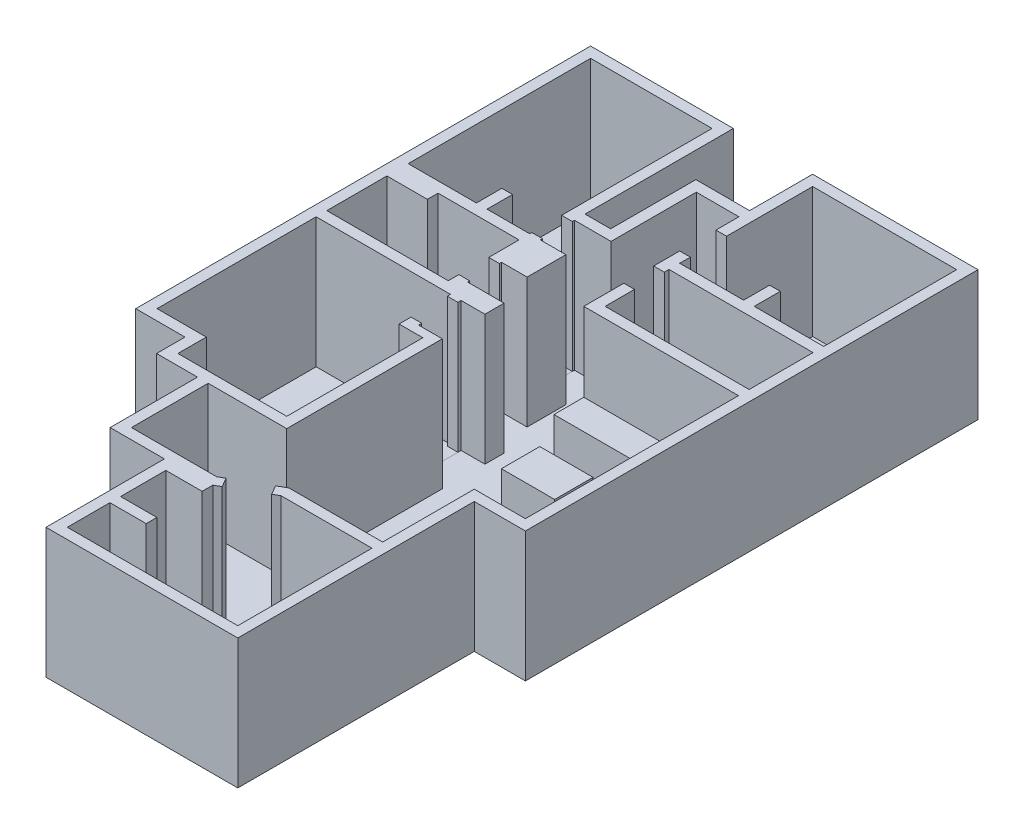
SolidWorks part; units mm, degrees
other "Long Room Closet"
other "Window Room Closet"
other "Walls"
other "Window Room"
other "Big Room"
other "Bathroom 1"
other "Corner Room"
other "Long Room"
other "Bathroom 2"
other "Big Room Closet"
other "Corner Room Closet"
ref_plane "Front Plane" through (0, 0, 0) normal (0, 0, 1) x (1, 0, 0)
ref_plane "Top Plane" through (0, 0, 0) normal (0, 1, 0) x (1, 0, 0)
ref_plane "Right Plane" through (0, 0, 0) normal (1, 0, 0) x (0, 0, -1)
sketch "Sketch1" plane through (0, 0, 0) normal (0, 1, 0) x (1, 0, 0)
  line L0 (0, 0) -> (0, -4280)
  line L1 (0, 0) -> (8590, 0) construction
  line L2 (0, 0) -> (0, -15669) construction
  line L3 (0, -15669) -> (8590, -15669) construction
  line L4 (8590, 0) -> (8590, -15669) construction
  line L5 (0, -4280) -> (1600, -4280)
  line L6 (1600, -4280) -> (1600, -3683)
  line L7 (1600, -3683) -> (1850, -3683)
  line L8 (2850, 0) -> (2850, -3530)
  line L9 (2850, -3530) -> (3100, -3530)
  line L11 (6710, -2510) -> (6710, -3120)
  line L12 (6710, -3120) -> (5210, -3120)
  line L13 (5210, -3480) -> (5210, -3370)
  line L14 (2850, 0) -> (0, 0)
  line L15 (5210, 0) -> (8590, 0)
  line L16 (8590, 0) -> (8590, -3120)
  line L17 (4241, -13106.5805) -> (4241, -13356.5805)
  line L18 (4116, -12890.0742) -> (4255.9329, -12809.2839)
  line L22 (8590, -3370) -> (8590, -4870)
  line L23 (5210, -4870) -> (8590, -4870)
  line L25 (0, -6190) -> (2850, -6190)
  line L26 (2850, -6190) -> (2850, -5940)
  line L27 (2850, -4530) -> (950, -4530)
  line L28 (0, -4780) -> (0, -6190)
  line L29 (950, -4530) -> (950, -4780)
  line L30 (1600, -3683) -> (0, -3683)
  line L31 (4255.9329, -12809.2839) -> (4380.9329, -13025.7903)
  line L32 (4241, -14419) -> (3390, -14419)
  line L33 (1850, -3683) -> (1850, -4280)
  line L34 (1850, -4280) -> (2850, -4280)
  line L35 (2850, -4280) -> (2850, -4230)
  line L36 (2850, -4230) -> (3100, -4230)
  line L37 (3100, -4230) -> (3100, -4280)
  line L38 (3100, -4280) -> (3700, -4280)
  line L39 (3100, -3530) -> (3100, -3480)
  line L40 (3100, -3480) -> (3960, -3480)
  line L41 (3960, -3480) -> (3960, -1480)
  line L42 (3960, -1480) -> (4960, -1480)
  line L43 (4960, -1480) -> (4960, -2020)
  line L45 (5210, -3120) -> (5210, -2870)
  line L46 (5210, -2870) -> (4960, -2870)
  line L47 (4960, -2870) -> (4960, -3480)
  line L48 (4960, -3480) -> (5210, -3480)
  line L49 (5210, -3480) -> (5210, -3370)
  line L50 (5210, -3370) -> (8590, -3370)
  line L51 (3700, -4280) -> (3700, -5190)
  line L52 (4960, -4180) -> (5210, -4180)
  line L53 (5210, -4180) -> (5210, -4870)
  line L54 (4960, -4180) -> (4960, -5120)
  line L55 (4960, -5120) -> (8590, -5120)
  line L56 (3700, -5190) -> (3100, -5190)
  line L57 (3100, -5190) -> (3100, -5240)
  line L58 (3100, -5240) -> (2850, -5240)
  line L59 (2850, -5240) -> (2850, -4530)
  line L60 (2850, -5940) -> (3100, -5940)
  line L61 (950, -4780) -> (0, -4780)
  line L62 (3100, -5940) -> (3100, -5990)
  line L63 (3100, -5990) -> (3960, -5990)
  line L64 (3960, -5990) -> (3960, -6440)
  line L65 (3960, -6440) -> (3401.2, -6440)
  line L66 (3401.2, -6440) -> (3401.2, -6515)
  line L67 (3401.2, -6515) -> (3151.2, -6515)
  line L68 (3151.2, -6515) -> (3151.2, -6440)
  line L69 (3151.2, -6440) -> (0, -6440)
  line L70 (1155.7, -10840.0742) -> (3710, -10840.0742)
  line L71 (3401.2, -7440) -> (3401.2, -7365)
  line L72 (3401.2, -7440) -> (3960, -7440)
  line L73 (3960, -7440) -> (3960, -11090.0742)
  line L74 (4380.9329, -13025.7903) -> (4241, -13106.5805)
  line L75 (3390, -14669) -> (4241, -14669)
  line L77 (4241, -14419) -> (4241, -14669)
  line L78 (3390, -14669) -> (3390, -15669)
  line L79 (3401.2, -7365) -> (3151.2, -7365)
  line L80 (3151.2, -7365) -> (3151.2, -7646.5)
  line L81 (3151.2, -7646.5) -> (3710, -7646.5)
  line L82 (3710, -7646.5) -> (3710, -10840.0742)
  line L83 (4116, -12890.0742) -> (2116, -12890.0742)
  line L84 (3960, -11090.0742) -> (2116, -11090.0742)
  line L86 (5117.0544, -12600.7903) -> (4992.0544, -12384.2839)
  line L89 (4992.0544, -12384.2839) -> (5190, -12270)
  line L90 (5190, -12270) -> (7390, -12270)
  line L91 (4255.9329, -12809.2839) -> (4992.0544, -12384.2839)
  line L92 (5117.0544, -12600.7903) -> (5256.9873, -12520)
  line L93 (5256.9873, -12520) -> (7390, -12520)
  line L94 (4241, -13356.5805) -> (3390, -13356.5805)
  line L95 (3390, -13356.5805) -> (3390, -14419)
  line L96 (4241, -13356.5805) -> (4241, -14419)
  line L97 (2116, -12890.0742) -> (2116, -11090.0742)
  line L98 (6710, -2510) -> (6960, -2510)
  line L99 (6960, -2510) -> (6960, -3120)
  line L100 (6960, -3120) -> (8590, -3120)
  line L101 (6960, -2510) -> (8590, -2510)
  line L102 (5210, -2020) -> (4960, -2020)
  line L103 (5210, -2020) -> (5210, 0)
  line L104 (4960, -2870) -> (4960, -3480)
  line L105 (5210, -3120) -> (5210, -2870)
  line L106 (8590, -5120) -> (8590, -10120)
  line L107 (8590, -10120) -> (7390, -10120)
  line L108 (7390, -10120) -> (7390, -12270)
  line L109 (7390, -12520) -> (7390, -15669)
  line L110 (7390, -15669) -> (3390, -15669)
  line L111 (4241, -13106.5805) -> (4116, -12890.0742) construction
  line L112 (3710, -10173.8) -> (0, -10173.8)
  line L113 (1155.7, -10840.0742) -> (1155.7, -10173.8)
  line L114 (0, -6440) -> (0, -10173.8)
  line L115 (1155.7, -10173.8) -> (0, -10173.8)
  line L116 (3401.2, -7365) -> (3401.2, -6515)
  line L117 (3100, -5940) -> (3100, -5240)
  line L118 (3100, -4230) -> (3100, -3530)
  line L119 (4960, -2870) -> (4960, -2020)
  line L120 (4960, -4180) -> (4960, -3480)
  dimension "D1" = 2850
  dimension "D2" = 150
  dimension "D3" = 4280
  dimension "D4" = 800
  dimension "D5" = 1000
  dimension "D6" = 600
  dimension "D7" = 860
  dimension "D8" = 1000
  dimension "D9" = 2000
  dimension "D10" = 250
  dimension "D11" = 250
  dimension "D12" = 250
  dimension "D13" = 558.8
  dimension "D14" = 250
  dimension "D15" = 250
  dimension "D16" = 3120
  dimension "D17" = 250
  dimension "D18" = 700
  dimension "D19" = 850
  dimension "D20" = 700
  dimension "D21" = 1500
  dimension "D22" = 3380
  dimension "D23" = 250
  dimension "D24" = 1500
  dimension "D25" = 1660
  dimension "D26" = 250
  dimension "D27" = 1206.5
  dimension "D28" = 5000
  dimension "D29" = 1000
  dimension "D30" = 250
  dimension "D31" = 3683
  dimension "D32" = 2510
  dimension "D33" = 450
  dimension "D34" = 250
  dimension "D35" = 4000
  dimension "D36" = 250
  dimension "D37" = 250
  dimension "D38" = 1200
  dimension "D39" = 2150
  dimension "D40" = 3149
  dimension "D41" = 3149
  dimension "D42" = 850
  dimension "D43" = 1000
  dimension "D44" = 250
  dimension "D45" = 2200
  dimension "D46" = 2000
  dimension "D47" = 1800
  dimension "D48" = 250
  dimension "D49" = 250
  dimension "D50" = 1900
  dimension "D51" = 700
  dimension "D52" = 250
  dimension "D53" = 850
  dimension "D54" = 2527.3
  dimension "D55" = 1155.7
extrude "Boss-Extrude1" add sketch "Sketch1" along normal blind 100 contours L36 L118 L9 L8 L14 L0 L5 L6 L7 L33 L34 L35 | L119 L46 L45 L12 L11 L98 L99 L100 L16 L15 L103 L102 | L60 L117 L58 L59 L27 L29 L61 L28 L25 L26 | L79 L116 L67 L68 L69 L114 L115 L113 L70 L82 L81 L80 | L110 L109 L93 L92 L86 L91 L31 L74 L17 L94 L95 L32 L77 L75 L78 | L120 L52 L53 L23 L22 L50 L13 L48 region at (1498.0773, 0, 1986.5335) region at (6770.383, 0, 1429.8229) region at (1531.4314, 0, 5404.487) region at (6839.4423, 0, 4110.3241) region at (1798.2254, 0, 8348.8303) region at (5668.1773, 0, 14190.9305)
extrude "Boss-Extrude2" add sketch "Sketch1<4>" along normal blind 100 separate body contours L54 L120 L47 L119 L43 L42 L41 L40 L39 L118 L37 L38 L51 L56 L57 L117 L62 L63 L64 L65 L66 L116 L71 L72 L73 L84 L97 L83 L18 L91 L89 L90 L108 L107 L106 L55 region at (5566.5772, 0, 8174.0459)
sketch "Sketch1<4>" plane through (0, 0, 0) normal (0, 1, 0) x (1, 0, 0) same geometry as "Sketch1"
extrude "Boss-Extrude4" add sketch "Sketch1<5>" along normal blind 100 separate body contours L6 L30 L0 L5 | L101 L99 L100 L16 | L113 L70 L82 L112 | L96 L94 L95 L32 region at (800, 0, 3981.5) region at (7775, 0, 2815) region at (2432.85, 0, 10506.9371) region at (3815.5, 0, 13887.7903)
sketch "Sketch1<5>" plane through (0, 0, 0) normal (0, 1, 0) x (1, 0, 0) same geometry as "Sketch1"
sketch "Sketch2" plane through (0, 100, 0) normal (0, 1, 0) x (1, 0, 0)
  line L0 (5210, -2020) -> (4960, -2020) construction
  line L1 (5210, -2020) -> (5210, 0) construction
  line L2 (5210, 0) -> (8590, 0) construction
  line L3 (8590, 0) -> (8590, -3120) construction
  line L4 (6960, -3120) -> (8590, -3120) construction
  line L5 (6960, -2510) -> (6960, -3120) construction
  line L6 (6710, -2510) -> (6960, -2510) construction
  line L7 (6710, -2510) -> (6710, -3120) construction
  line L8 (6710, -3120) -> (5210, -3120) construction
  line L9 (5210, -3120) -> (5210, -2870) construction
  line L10 (5210, -3120) -> (5210, -2870) construction
  line L11 (2850, -3530) -> (3100, -3530) construction
  line L12 (2850, 0) -> (2850, -3530) construction
  line L13 (2850, 0) -> (0, 0) construction
  line L14 (0, 0) -> (0, -4280) construction
  line L15 (0, -4280) -> (1600, -4280) construction
  line L16 (1600, -4280) -> (1600, -3683) construction
  line L17 (1600, -3683) -> (1850, -3683) construction
  line L18 (1850, -3683) -> (1850, -4280) construction
  line L19 (1850, -4280) -> (2850, -4280) construction
  line L20 (2850, -4280) -> (2850, -4230) construction
  line L21 (2850, -4230) -> (3100, -4230) construction
  line L22 (3100, -3530) -> (3100, -3480) construction
  line L23 (3100, -3480) -> (3960, -3480) construction
  line L24 (3960, -3480) -> (3960, -1480) construction
  line L25 (3960, -1480) -> (4960, -1480) construction
  line L26 (4960, -1480) -> (4960, -2020) construction
  line L27 (3100, -4230) -> (3100, -3530) construction
  line L28 (4116, -12890.0742) -> (4255.9329, -12809.2839) construction
  line L29 (4116, -12890.0742) -> (2116, -12890.0742) construction
  line L30 (2116, -12890.0742) -> (2116, -11090.0742) construction
  line L31 (3960, -11090.0742) -> (2116, -11090.0742) construction
  line L32 (3960, -7440) -> (3960, -11090.0742) construction
  line L33 (3401.2, -7440) -> (3960, -7440) construction
  line L34 (3401.2, -7440) -> (3401.2, -7365) construction
  line L35 (4255.9329, -12809.2839) -> (4380.9329, -13025.7903) construction
  line L36 (4380.9329, -13025.7903) -> (4241, -13106.5805) construction
  line L37 (4241, -13106.5805) -> (4241, -13356.5805) construction
  line L38 (4241, -13356.5805) -> (3390, -13356.5805) construction
  line L39 (3390, -13356.5805) -> (3390, -14419) construction
  line L40 (4241, -14419) -> (3390, -14419) construction
  line L41 (4241, -14419) -> (4241, -14669) construction
  line L42 (3390, -14669) -> (4241, -14669) construction
  line L43 (3390, -14669) -> (3390, -15669) construction
  line L44 (7390, -15669) -> (3390, -15669) construction
  line L45 (7390, -12520) -> (7390, -15669) construction
  line L46 (5256.9873, -12520) -> (7390, -12520) construction
  line L47 (5117.0544, -12600.7903) -> (5256.9873, -12520) construction
  line L48 (5117.0544, -12600.7903) -> (4992.0544, -12384.2839) construction
  line L49 (4255.9329, -12809.2839) -> (4992.0544, -12384.2839) construction
  line L50 (4960, -2870) -> (4960, -3480) construction
  line L51 (4960, -3480) -> (5210, -3480) construction
  line L52 (4960, -2870) -> (4960, -3480) construction
  line L53 (4960, -4180) -> (4960, -3480) construction
  line L54 (5210, -2870) -> (4960, -2870) construction
  line L55 (4960, -2870) -> (4960, -2020) construction
  line L56 (3100, -4230) -> (3100, -4280) construction
  line L57 (3100, -4280) -> (3700, -4280) construction
  line L58 (3700, -4280) -> (3700, -5190) construction
  line L59 (3700, -5190) -> (3100, -5190) construction
  line L60 (3100, -5190) -> (3100, -5240) construction
  line L61 (5210, -3480) -> (5210, -3370) construction
  line L62 (5210, -3480) -> (5210, -3370) construction
  line L63 (4960, -4180) -> (5210, -4180) construction
  line L64 (5210, -4180) -> (5210, -4870) construction
  line L65 (5210, -4870) -> (8590, -4870) construction
  line L66 (8590, -3370) -> (8590, -4870) construction
  line L67 (5210, -3370) -> (8590, -3370) construction
  line L68 (2850, -5940) -> (3100, -5940) construction
  line L69 (2850, -6190) -> (2850, -5940) construction
  line L70 (0, -6190) -> (2850, -6190) construction
  line L71 (0, -4780) -> (0, -6190) construction
  line L72 (950, -4780) -> (0, -4780) construction
  line L73 (950, -4530) -> (950, -4780) construction
  line L74 (2850, -4530) -> (950, -4530) construction
  line L75 (2850, -5240) -> (2850, -4530) construction
  line L76 (3100, -5240) -> (2850, -5240) construction
  line L77 (3100, -5940) -> (3100, -5240) construction
  line L78 (4960, -4180) -> (4960, -5120) construction
  line L79 (4960, -5120) -> (8590, -5120) construction
  line L80 (8590, -5120) -> (8590, -10120) construction
  line L81 (8590, -10120) -> (7390, -10120) construction
  line L82 (7390, -10120) -> (7390, -12270) construction
  line L83 (5190, -12270) -> (7390, -12270) construction
  line L84 (4992.0544, -12384.2839) -> (5190, -12270) construction
  line L85 (3100, -5940) -> (3100, -5990) construction
  line L86 (3100, -5990) -> (3960, -5990) construction
  line L87 (3960, -5990) -> (3960, -6440) construction
  line L88 (3960, -6440) -> (3401.2, -6440) construction
  line L89 (3401.2, -6440) -> (3401.2, -6515) construction
  line L90 (3401.2, -7365) -> (3151.2, -7365) construction
  line L91 (3151.2, -7365) -> (3151.2, -7646.5) construction
  line L92 (3151.2, -7646.5) -> (3710, -7646.5) construction
  line L93 (3710, -7646.5) -> (3710, -10840.0742) construction
  line L94 (1155.7, -10840.0742) -> (3710, -10840.0742) construction
  line L95 (1155.7, -10840.0742) -> (1155.7, -10173.8) construction
  line L96 (1155.7, -10173.8) -> (0, -10173.8) construction
  line L97 (0, -6440) -> (0, -10173.8) construction
  line L98 (3151.2, -6440) -> (0, -6440) construction
  line L99 (3151.2, -6515) -> (3151.2, -6440) construction
  line L100 (3401.2, -6515) -> (3151.2, -6515) construction
  line L101 (3401.2, -7365) -> (3401.2, -6515) construction
  line L102 (5210, -2020) -> (4960, -2020)
  line L103 (5210, -2020) -> (5210, 0)
  line L104 (5210, 0) -> (8590, 0)
  line L105 (8590, 0) -> (8590, -3120)
  line L106 (6960, -3120) -> (8590, -3120)
  line L107 (6960, -2510) -> (6960, -3120)
  line L108 (6710, -2510) -> (6960, -2510)
  line L109 (6710, -2510) -> (6710, -3120)
  line L110 (6710, -3120) -> (5210, -3120)
  line L111 (5210, -3120) -> (5210, -2870)
  line L112 (5210, -3120) -> (5210, -2870)
  line L113 (2850, -3530) -> (3100, -3530)
  line L114 (2850, 0) -> (2850, -3530)
  line L115 (2850, 0) -> (0, 0)
  line L116 (0, 0) -> (0, -4280)
  line L117 (0, -4280) -> (1600, -4280)
  line L118 (1600, -4280) -> (1600, -3683)
  line L119 (1600, -3683) -> (1850, -3683)
  line L120 (1850, -3683) -> (1850, -4280)
  line L121 (1850, -4280) -> (2850, -4280)
  line L122 (2850, -4280) -> (2850, -4230)
  line L123 (2850, -4230) -> (3100, -4230)
  line L124 (3100, -3530) -> (3100, -3480)
  line L125 (3100, -3480) -> (3960, -3480)
  line L126 (3960, -3480) -> (3960, -1480)
  line L127 (3960, -1480) -> (4960, -1480)
  line L128 (4960, -1480) -> (4960, -2020)
  line L129 (3100, -4230) -> (3100, -3530)
  line L130 (4116, -12890.0742) -> (4255.9329, -12809.2839)
  line L131 (4116, -12890.0742) -> (2116, -12890.0742)
  line L132 (2116, -12890.0742) -> (2116, -11090.0742)
  line L133 (3960, -11090.0742) -> (2116, -11090.0742)
  line L134 (3960, -7440) -> (3960, -11090.0742)
  line L135 (3401.2, -7440) -> (3960, -7440)
  line L136 (3401.2, -7440) -> (3401.2, -7365)
  line L137 (4255.9329, -12809.2839) -> (4380.9329, -13025.7903)
  line L138 (4380.9329, -13025.7903) -> (4241, -13106.5805)
  line L139 (4241, -13106.5805) -> (4241, -13356.5805)
  line L140 (4241, -13356.5805) -> (3390, -13356.5805)
  line L141 (3390, -13356.5805) -> (3390, -14419)
  line L142 (4241, -14419) -> (3390, -14419)
  line L143 (4241, -14419) -> (4241, -14669)
  line L144 (3390, -14669) -> (4241, -14669)
  line L145 (3390, -14669) -> (3390, -15669)
  line L146 (7390, -15669) -> (3390, -15669)
  line L147 (7390, -12520) -> (7390, -15669)
  line L148 (5256.9873, -12520) -> (7390, -12520)
  line L149 (5117.0544, -12600.7903) -> (5256.9873, -12520)
  line L150 (5117.0544, -12600.7903) -> (4992.0544, -12384.2839)
  line L151 (4255.9329, -12809.2839) -> (4992.0544, -12384.2839)
  line L152 (4960, -2870) -> (4960, -3480)
  line L153 (4960, -3480) -> (5210, -3480)
  line L154 (4960, -2870) -> (4960, -3480)
  line L155 (4960, -4180) -> (4960, -3480)
  line L156 (5210, -2870) -> (4960, -2870)
  line L157 (4960, -2870) -> (4960, -2020)
  line L158 (3100, -4230) -> (3100, -4280)
  line L159 (3100, -4280) -> (3700, -4280)
  line L160 (3700, -4280) -> (3700, -5190)
  line L161 (3700, -5190) -> (3100, -5190)
  line L162 (3100, -5190) -> (3100, -5240)
  line L163 (5210, -3480) -> (5210, -3370)
  line L164 (5210, -3480) -> (5210, -3370)
  line L165 (4960, -4180) -> (5210, -4180)
  line L166 (5210, -4180) -> (5210, -4870)
  line L167 (5210, -4870) -> (8590, -4870)
  line L168 (8590, -3370) -> (8590, -4870)
  line L169 (5210, -3370) -> (8590, -3370)
  line L170 (2850, -5940) -> (3100, -5940)
  line L171 (2850, -6190) -> (2850, -5940)
  line L172 (0, -6190) -> (2850, -6190)
  line L173 (0, -4780) -> (0, -6190)
  line L174 (950, -4780) -> (0, -4780)
  line L175 (950, -4530) -> (950, -4780)
  line L176 (2850, -4530) -> (950, -4530)
  line L177 (2850, -5240) -> (2850, -4530)
  line L178 (3100, -5240) -> (2850, -5240)
  line L179 (3100, -5940) -> (3100, -5240)
  line L180 (4960, -4180) -> (4960, -5120)
  line L181 (4960, -5120) -> (8590, -5120)
  line L182 (8590, -5120) -> (8590, -10120)
  line L183 (8590, -10120) -> (7390, -10120)
  line L184 (7390, -10120) -> (7390, -12270)
  line L185 (5190, -12270) -> (7390, -12270)
  line L186 (4992.0544, -12384.2839) -> (5190, -12270)
  line L187 (3100, -5940) -> (3100, -5990)
  line L188 (3100, -5990) -> (3960, -5990)
  line L189 (3960, -5990) -> (3960, -6440)
  line L190 (3960, -6440) -> (3401.2, -6440)
  line L191 (3401.2, -6440) -> (3401.2, -6515)
  line L192 (3401.2, -7365) -> (3151.2, -7365)
  line L193 (3151.2, -7365) -> (3151.2, -7646.5)
  line L194 (3151.2, -7646.5) -> (3710, -7646.5)
  line L195 (3710, -7646.5) -> (3710, -10840.0742)
  line L196 (1155.7, -10840.0742) -> (3710, -10840.0742)
  line L197 (1155.7, -10840.0742) -> (1155.7, -10173.8)
  line L198 (1155.7, -10173.8) -> (0, -10173.8)
  line L199 (0, -6440) -> (0, -10173.8)
  line L200 (3151.2, -6440) -> (0, -6440)
  line L201 (3151.2, -6515) -> (3151.2, -6440)
  line L202 (3401.2, -6515) -> (3151.2, -6515)
  line L203 (3401.2, -7365) -> (3401.2, -6515)
  line L204 (-250, -10423.8) -> (905.7, -10423.8)
  line L205 (905.7, -10423.8) -> (905.7, -11090.0742)
  line L206 (905.7, -11090.0742) -> (1866, -11090.0742)
  line L207 (1866, -11090.0742) -> (1866, -13140.0742)
  line L208 (1866, -13140.0742) -> (3140, -13140.0742)
  line L209 (3140, -13140.0742) -> (3140, -15919)
  line L210 (8840, -10370) -> (7640, -10370)
  line L211 (7640, -10370) -> (7640, -15919)
  line L212 (4960, 250) -> (4960, -1230)
  line L213 (4960, -1230) -> (3700, -1230)
  line L214 (-250, 250) -> (3100, 250)
  line L215 (-250, 250) -> (-250, -10423.8)
  line L216 (3140, -15919) -> (7640, -15919)
  line L217 (8840, 250) -> (8840, -10370)
  line L218 (3700, -1230) -> (3700, -3230)
  line L219 (3700, -3230) -> (3100, -3230)
  line L220 (3100, -3230) -> (3100, 250)
  line L221 (4960, 250) -> (8840, 250)
  line M1 (4960, -5120) -> (4960, -1480)
  line M2 (4960, -1480) -> (3960, -1480)
  line M3 (3960, -1480) -> (3960, -3480)
  line M4 (3960, -3480) -> (3100, -3480)
  line M5 (3100, -3480) -> (3100, -4280)
  line M6 (3100, -4280) -> (3700, -4280)
  line M7 (3700, -4280) -> (3700, -5190)
  line M8 (3700, -5190) -> (3100, -5190)
  line M9 (3100, -5190) -> (3100, -5990)
  line M10 (3100, -5990) -> (3960, -5990)
  line M11 (3960, -5990) -> (3960, -6440)
  line M12 (3960, -6440) -> (3401.2, -6440)
  line M13 (3401.2, -6440) -> (3401.2, -7440)
  dimension "D1" = 250
  dimension "D2" = 250
  dimension "D3" = 250
  dimension "D4" = 250
  dimension "D5" = 250
  dimension "D6" = 250
  dimension "D7" = 250
  dimension "D8" = 250
  dimension "D9" = 250
  dimension "D10" = 250
  dimension "D11" = 250
  dimension "D12" = 250
  dimension "D13" = 250
  dimension "D14" = 250
  dimension "D15" = 250
  dimension "D16" = 250
extrude "Boss-Extrude3" add sketch "Sketch2" along normal blind 3048 separate body contours L217 L214 L215 L216 L202 L170 L171 L172 L173 L174 L175 L176 L177 L178 L123 L122 L121 L120 L119 L118 L117 L116 L115 L114 L113 L102 L103 L104 L105 L106 L107 L108 L109 L110 L111 M13 M12 M11 M10 M9 M8 M7 M6 M5 M4 M3 M2 M1 region at (-64.5102, 100, 5086.9)
sketch "Sketch5" plane through (0, 100, 0) normal (0, 1, 0) x (1, 0, 0)
  line L0 (8590, -7120) -> (7890, -7120)
  line L1 (5444.7619, -6637.9805) -> (6694.7619, -6637.9805)
  line L2 (5444.7619, -6637.9805) -> (5444.7619, -7537.9805)
  line L3 (5444.7619, -7537.9805) -> (6694.7619, -7537.9805)
  line L4 (6694.7619, -6637.9805) -> (6694.7619, -7537.9805)
  line L5 (8590, -10120) -> (8590, -5120) construction
  line L6 (7890, -7120) -> (7890, -5820)
  line L7 (7890, -5820) -> (4960, -5820)
  line L8 (4960, -5820) -> (4960, -5120)
  line L9 (4960, -5120) -> (8590, -5120)
  line L10 (8590, -5120) -> (8590, -7120)
  line L11 (0, -6190) -> (2850, -6190) construction
  line L12 (0, -4780) -> (950, -4780)
  line L13 (0, -4780) -> (0, -6190)
  line L14 (0, -6190) -> (950, -6190)
  line L15 (950, -4780) -> (950, -6190)
  line L16 (5210, -3370) -> (8590, -3370) construction
  line L17 (8590, -4870) -> (7640, -4870)
  line L18 (8590, -4870) -> (8590, -3370)
  line L19 (8590, -3370) -> (7640, -3370)
  line L20 (7640, -4870) -> (7640, -3370)
  line L21 (8490, -4770) -> (8490, -3470)
  line L22 (8490, -3470) -> (7740, -3470)
  line L23 (7740, -4770) -> (7740, -3470)
  line L24 (8490, -4770) -> (7740, -4770)
  line L25 (100, -4880) -> (100, -6090)
  line L26 (100, -6090) -> (850, -6090)
  line L27 (850, -4880) -> (850, -6090)
  line L28 (100, -4880) -> (850, -4880)
  line M41 (8590, -10120) -> (8590, -5120)
  line M42 (8590, -5120) -> (4960, -5120)
  dimension "D1" = 900
  dimension "D2" = 1250
  dimension "D3" = 2000
  dimension "D4" = 700
  dimension "D5" = 700
  dimension "D6" = 100
extrude "Boss-Extrude7" add sketch "Sketch5" along normal blind 1200 contours L4 L1 L2 L3 | L8 L7 L6 L0 M41 M42 region at (7161.3083, 100, 5733.6917) region at (6069.7619, 100, 7087.9805)
extrude "Boss-Extrude9" add sketch "Sketch5<3>" along normal blind 800 contours L15 L12 L13 L14 L25 L28 L27 L26 region at (475, 100, 4797.0018)
sketch "Sketch5<3>" plane through (0, 100, 0) normal (0, 1, 0) x (1, 0, 0) same geometry as "Sketch5"
extrude "Boss-Extrude10" add sketch "Sketch5<4>" along normal blind 800 contours L20 L17 L18 L19 L21 L24 L23 L22 region at (8115, 100, 4852.2447)
sketch "Sketch5<4>" plane through (0, 100, 0) normal (0, 1, 0) x (1, 0, 0) same geometry as "Sketch5"
